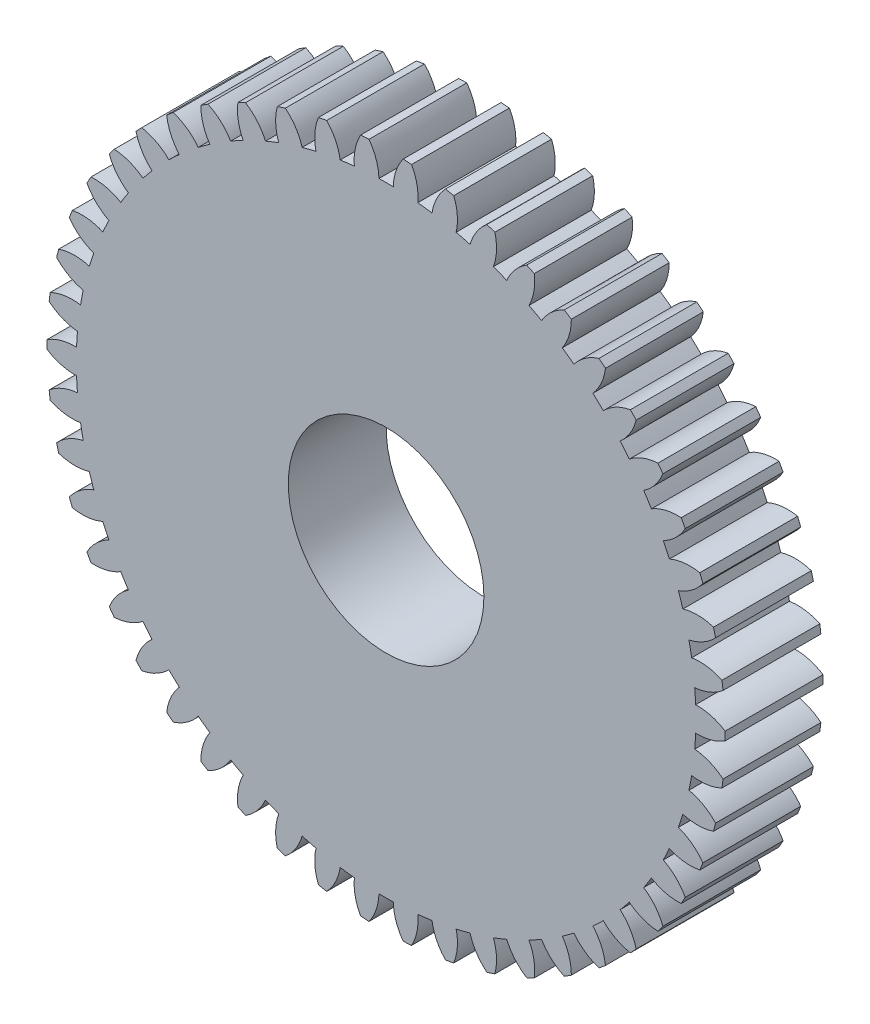
SolidWorks part; units mm, degrees
ref_plane "Front Plane" through (0, 0, 0) normal (0, 0, 1) x (1, 0, 0)
ref_plane "Top Plane" through (0, 0, 0) normal (0, 1, 0) x (1, 0, 0)
ref_plane "Right Plane" through (0, 0, 0) normal (1, 0, 0) x (0, 0, -1)
sketch "Sketch1" plane through (0, 0, 0) normal (0, 0, 1) x (1, 0, 0)
  circle A0 centre (0, 0) radius 50
  circle A1 centre (0, 0) radius 52
  circle A2 centre (0, 0) radius 47.5
  dimension "D1" = 100
  dimension "D2" = 104
  dimension "D3" = 4.5
extrude "Boss-Extrude3" add sketch "Sketch1" along normal mid plane 15 contours A1
sketch "Sketch3" plane through (0, 0, 0) normal (0, 0, 1) x (1, 0, 0)
  line L0 (0, 0) -> (0, 52) construction
  line L1 (-1.5705, 49.9753) -> (1.5705, 49.9753) construction
  line L2 (-1.102, 47.4872) -> (0, 0)
  line L3 (0, 45.6603) -> (-2.6473, 52.9338) construction
  line L4 (0, 0) -> (3.2651, 51.8974) construction
  line L5 (1.5705, 49.9753) -> (4.7054, 49.7781) construction
  circle A0 centre (0, 0) radius 52 construction
  arc A1 (-3.4495, 52.8876) -> (-1.102, 47.4872) centre (-8.904, 47.3062) cw
  circle A2 centre (0, 0) radius 47.5 construction
  arc A3 (3.4495, 52.8876) -> (1.102, 47.4872) centre (8.904, 47.3062) ccw
  arc A4 (1.102, 47.4872) -> (-1.102, 47.4872) centre (0, 0) ccw
  circle A8 centre (0, 0) radius 50 construction
  circle A9 centre (0, 0) radius 53
  arc A10 (3.4495, 52.8876) -> (-3.4495, 52.8876) centre (0, 0) ccw
  circle A11 centre (0, 0) radius 52 construction
  dimension "D2" = 20
  dimension "D3" = 3.6
  dimension "D1" = 1
sketch "Sketch4" plane through (0, 0, 0) normal (0, 1, 0) x (1, 0, 0)
  line L0 (0, -7.5) -> (0, 7.5)
  line L1 (-52, -7.5) -> (52, -7.5) construction
  line L2 (52, 7.5) -> (-52, 7.5) construction
curve "Curve1"
sketch "Sketch5" plane through (0, 0, 7.5) normal (0, 0, 1) x (1, 0, 0)
  line L0 (0, 0) -> (0, 52) construction
  line L1 (-1.5705, 49.9753) -> (1.5705, 49.9753) construction
  line L2 (-1.102, 47.4872) -> (0, 0)
  line L3 (0, 45.6603) -> (-2.6473, 52.9338) construction
  line L4 (0, 0) -> (3.2651, 51.8974) construction
  line L5 (1.5705, 49.9753) -> (4.7054, 49.7781) construction
  arc A1 (-3.4495, 52.8876) -> (-1.102, 47.4872) centre (-8.904, 47.3062) cw
  arc A3 (3.4495, 52.8876) -> (1.102, 47.4872) centre (8.904, 47.3062) ccw
  arc A4 (1.102, 47.4872) -> (-1.102, 47.4872) centre (0, 0) ccw
  arc A10 (3.4495, 52.8876) -> (-3.4495, 52.8876) centre (0, 0) ccw
sketch "Sketch6" plane through (0, 0, -7.5) normal (0, 0, 1) x (1, 0, 0)
  line L0 (0, 0) -> (0, 52) construction
  line L1 (-1.5705, 49.9753) -> (1.5705, 49.9753) construction
  line L2 (-1.102, 47.4872) -> (0, 0)
  line L3 (0, 45.6603) -> (-2.6473, 52.9338) construction
  line L4 (0, 0) -> (3.2651, 51.8974) construction
  line L5 (1.5705, 49.9753) -> (4.7054, 49.7781) construction
  arc A1 (-3.4495, 52.8876) -> (-1.102, 47.4872) centre (-8.904, 47.3062) cw
  arc A3 (3.4495, 52.8876) -> (1.102, 47.4872) centre (8.904, 47.3062) ccw
  arc A4 (1.102, 47.4872) -> (-1.102, 47.4872) centre (0, 0) ccw
  arc A10 (3.4495, 52.8876) -> (-3.4495, 52.8876) centre (0, 0) ccw
loft "Cut-Loft1" cut section "Sketch5" section "Sketch3" section "Sketch6" start constraint default end constraint default connector at (-3.4495, 52.8876, 7.5) connector at (-3.4495, 52.8876, 0) connector at (-3.4495, 52.8876, -7.5)
pattern_circular "CirPattern1" count 50 over 360 about axis through (0, 0, 7.5) along (0, 0, -1) of "Cut-Loft1" reverse direction yes
sketch "Sketch7" plane through (0, 0, 7.5) normal (0, 0, 1) x (1, 0, 0)
  circle A0 centre (0, 0) radius 15
  dimension "D1" = 30
extrude "Cut-Extrude1" cut sketch "Sketch7" against normal through all
equation "\"Module\"= 2"
equation "\"Number of Teeth\"= 50"
equation "\"D1@Sketch1\"= \"Module\" * \"Number of Teeth\""
equation "\"D2@Sketch1\"=(\"Number of Teeth\"+2) * \"Module\""
equation "\"D3@Sketch1\"=\"Module\" *  if(\"Module\"=>1.25,2.25,2.4)"
equation "\"D3@Sketch3\"= 180 / \"Number of Teeth\""
equation "\"D1@CirPattern1\"= \"Number of Teeth\""
